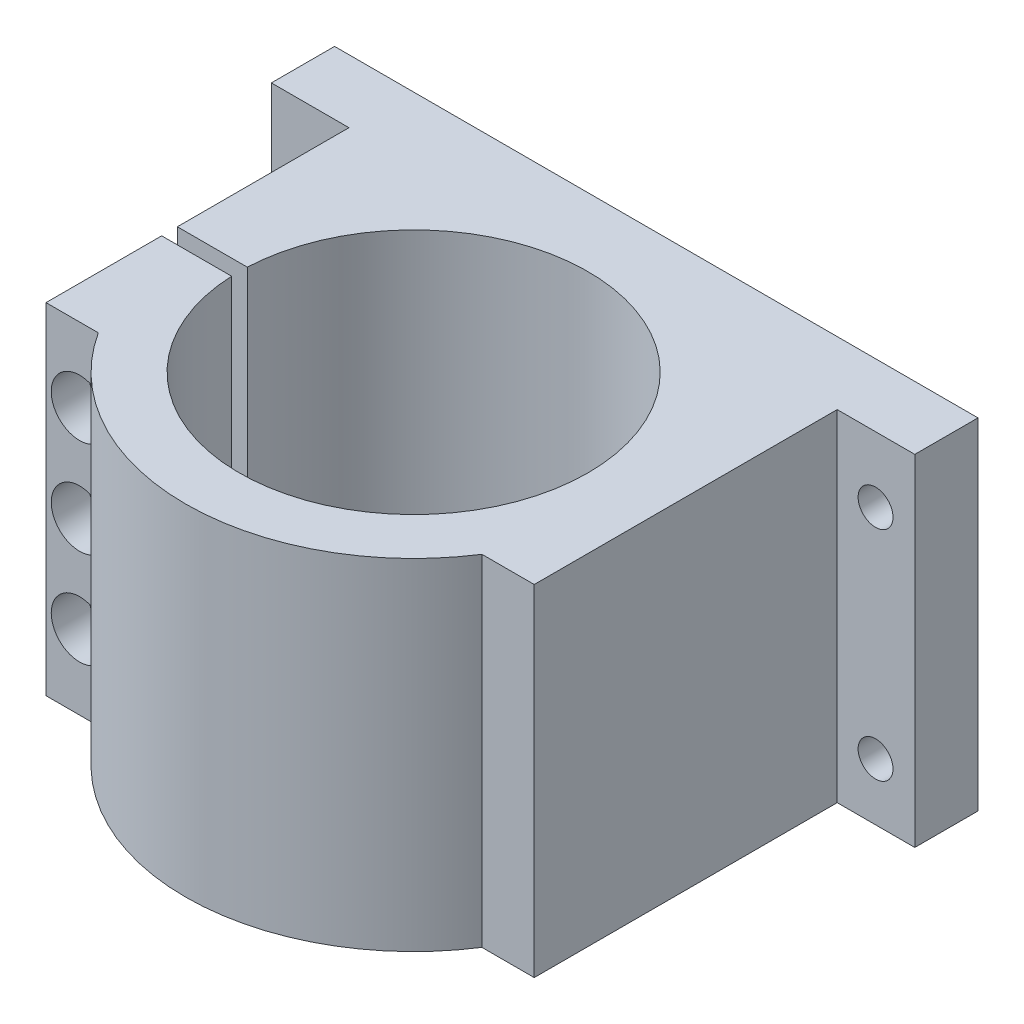
SolidWorks part; units mm, degrees
ref_plane "Front Plane" through (0, 0, 0) normal (0, 0, 1) x (1, 0, 0)
ref_plane "Top Plane" through (0, 0, 0) normal (0, 1, 0) x (1, 0, 0)
ref_plane "Right Plane" through (0, 0, 0) normal (1, 0, 0) x (0, 0, -1)
sketch "Sketch1" plane through (0, 0, 0) normal (0, 0, 1) x (1, 0, 0)
  line L1 (0, 0) -> (147.6, 0)
  line L2 (0, 0) -> (0, 78.1)
  line L3 (0, 78.1) -> (147.6, 78.1)
  line L4 (147.6, 0) -> (147.6, 78.1)
  dimension "D1" = 147.6
  dimension "D2" = 78.1
extrude "Boss-Extrude1" add sketch "Sketch1" along normal blind 14.5
sketch "Sketch2" plane through (0, 0, 14.5) normal (0, 0, 1) x (1, 0, 0)
  line L0 (73.8, 78.1) -> (73.8, 0) construction
  line L1 (147.6, 78.1) -> (0, 78.1) construction
  line L2 (0, 0) -> (147.6, 0) construction
  line L4 (17.8, 78.1) -> (129.8, 78.1)
  line L5 (17.8, 78.1) -> (17.8, 0)
  line L6 (17.8, 0) -> (129.8, 0)
  line L7 (129.8, 78.1) -> (129.8, 0)
  point P10 (73.8, 78.1)
  dimension "D1" = 112
extrude "Boss-Extrude2" add sketch "Sketch2" along normal blind 93.5
sketch "Sketch3" plane through (0, 78.1, 0) normal (0, 1, 0) x (1, 0, 0)
  line L0 (17.8, -84) -> (29.8, -84)
  line L1 (17.8, -108) -> (17.8, -14.5) construction
  line L2 (129.8, -84) -> (117.8, -84)
  line L3 (129.8, -108) -> (129.8, -14.5) construction
  line L4 (73.8, 0) -> (73.8, -108) construction
  line L5 (147.6, 0) -> (0, 0) construction
  line L6 (129.8, -108) -> (17.8, -108) construction
  line L7 (73.8, -55.6667) -> (17.8, -55.6667) construction
  line L8 (17.8, -53.8667) -> (33.8405, -53.8667)
  line L9 (17.8, -57.4667) -> (33.8405, -57.4667)
  arc A0 (29.8, -84) -> (117.8, -84) centre (73.8, -55.6667) ccw
  arc A1 (33.8405, -57.4667) -> (33.8405, -53.8667) centre (73.8, -55.6667) ccw
  line M6 (17.8, -14.5) -> (17.8, -108)
  line M7 (17.8, -108) -> (129.8, -108)
  line M8 (129.8, -108) -> (129.8, -14.5)
  dimension "D3" = 80
  dimension "D1" = 84
  dimension "D2" = 12
  dimension "D4" = 3.6
extrude "Cut-Extrude1" cut sketch "Sketch3" against normal up to next contours A0 L0 M6 M7 | A0 L2 M7 M8 | L4 A1 | A1 L4 region at (115.2584, 78.1, 98.708) region at (32.3416, 78.1, 98.708) region at (56.128, 78.1, 55.6667) region at (90.7765, 78.1, 55.6667)
sketch "Sketch4" plane through (0, 0, 84) normal (0, 0, 1) x (1, 0, 0)
  line L0 (25.5, 78.1) -> (25.5, 0) construction
  line L1 (17.8, 78.1) -> (29.8, 78.1) construction
  line L2 (29.8, 0) -> (17.8, 0) construction
  line L3 (17.8, 39.05) -> (29.8, 39.05) construction
  line L6 (17.8, 0) -> (17.8, 78.1) construction
  line L7 (29.8, 0) -> (29.8, 78.1) construction
  circle A0 centre (25.5, 61.05) radius 6.5
  circle A1 centre (25.5, 39.05) radius 6.5
  circle A2 centre (25.5, 17.05) radius 6.5
  point P8 (25.5, 61.05)
  point P12 (25.5, 39.05)
  dimension "D1" = 13
  dimension "D2" = 9
  dimension "D3" = 1.2
extrude "Cut-Extrude2" cut sketch "Sketch4" against normal blind 8.4 and the other way blind 8.4
sketch "Sketch5" plane through (0, 0, 75.6) normal (0, 0, 1) x (1, 0, 0)
  circle A0 centre (25.5, 61.05) radius 4
  circle A1 centre (25.5, 39.05) radius 4
  circle A2 centre (25.5, 17.05) radius 4
  dimension "D1" = 8
extrude "Cut-Extrude3" cut sketch "Sketch5" against normal up to next
sketch "Sketch7" plane through (0, 0, 0) normal (0, 0, -1) x (-1, 0, 0)
  line L0 (-73.8, 78.1) -> (-73.8, 0) construction
  line L1 (-147.6, 78.1) -> (0, 78.1) construction
  line L2 (0, 0) -> (-147.6, 0) construction
  line L3 (-9, 78.1) -> (-9, 0) construction
  line L4 (0, 78.1) -> (0, 0) construction
  circle A0 centre (-9, 63.1) radius 4
  circle A1 centre (-9, 13.1) radius 4
  circle A2 centre (-138.6, 13.1) radius 4
  circle A3 centre (-138.6, 63.1) radius 4
  dimension "D1" = 8
  dimension "D2" = 50
  dimension "D3" = 15
  dimension "D4" = 9
extrude "Cut-Extrude4" cut sketch "Sketch7" against normal through all
